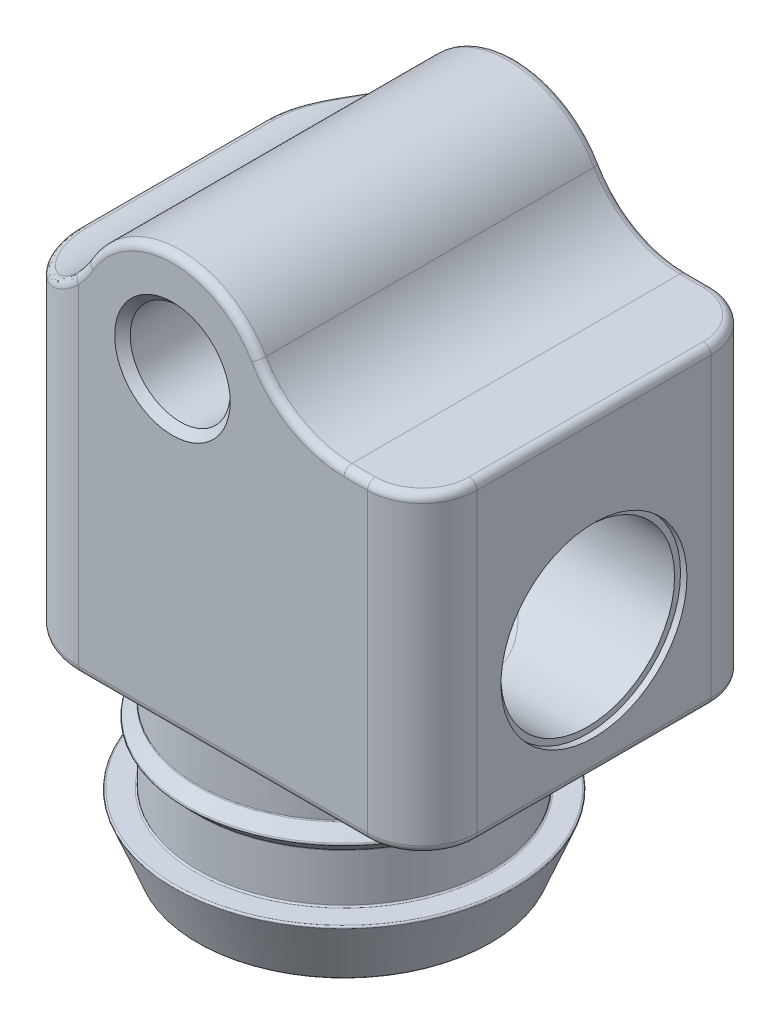
SolidWorks part; units mm, degrees
ref_plane "Front Plane" through (0, 0, 0) normal (0, 0, 1) x (1, 0, 0)
ref_plane "Top Plane" through (0, 0, 0) normal (0, 1, 0) x (1, 0, 0)
ref_plane "Right Plane" through (0, 0, 0) normal (1, 0, 0) x (0, 0, -1)
sketch "Sketch1" plane through (0, 0, 0) normal (0, 0, 1) x (1, 0, 0)
  line L4 (-11, 0) -> (-6.35, 0)
  line L5 (-11, 0) -> (-11, -20)
  line L6 (-11, -20) -> (16, -20)
  line L7 (16, 0) -> (16, -20)
  line L8 (6.35, 0) -> (16, 0)
  circle A0 centre (0, 0) radius 3.2
  arc A1 (6.35, 0) -> (-6.35, 0) centre (0, 0) ccw
  dimension "D1" = 6.4
  dimension "D2" = 12.7
  dimension "D3" = 11
  dimension "D4" = 16
  dimension "D5" = 20
extrude "Boss-Extrude1" add sketch "Sketch1" along normal mid plane 22
sketch3d "3DSketch1" plane through (0, 0, 0) normal (0, 0, 1) x (1, 0, 0)
  dimension "D1" = 12.7
sketch "Sketch2" plane through (0, 0, 0) normal (0, 0, 1) x (1, 0, 0)
  line L0 (0, 9.544) -> (0, -9.544) construction
  line L1 (0, -20) -> (9.365, -20)
  line L4 (0, -32.7) -> (9.365, -32.7)
  line L10 (0, -32.7) -> (0, -20)
  line L11 (9.365, -32.7) -> (10.9525, -28.7312)
  line L12 (10.9525, -28.7312) -> (9.365, -28.7312)
  line L13 (9.365, -28.7312) -> (9.365, -25.5563)
  line L14 (9.365, -25.5563) -> (10.1588, -24.7625)
  line L15 (10.1588, -24.7625) -> (9.365, -23.9688)
  line L16 (10.1588, -24.7625) -> (9.365, -24.7625) construction
  line L17 (9.365, -23.9688) -> (9.365, -20)
  dimension "D1" = 18.73
  dimension "D2" = 12.7
  dimension "D3" = 1.5875
  dimension "D4" = 3.9688
  dimension "D5" = 0.7937
  dimension "D6" = 7.9375
  dimension "D7" = 20
revolve "Revolve1" add sketch "Sketch2" angle 360 about L0
sketch "Sketch3" plane through (0, -32.7, 0) normal (0, -1, 0) x (1, 0, 0)
  circle A0 centre (0, 0) radius 6
  dimension "D1" = 12
extrude "Cut-Extrude1" cut sketch "Sketch3" against normal blind 27.25 contours A0
hole_wizard "1/4 NPT Tapped Hole1" positions "Sketch4" profile "Sketch5" size "1/4" standard "ANSI Inch" end condition up to next
sketch "Sketch4" plane through (16, 0, 0) normal (1, 0, 0) x (0, 0, -1)
  point P0 (0, -12)
  dimension "D1" = 12
cosmetic thread "Hole Thread1" parameters "D1"=0.4, "D2"=13.1394
sketch "Sketch5" plane through (16, -12, 0) normal (0, 1, 0) x (0, 0, -1)
  line L0 (0, 0) -> (0, 10)
  line L1 (0, 10) -> (5.5626, 10)
  line L2 (-5.9437, 0.4) -> (-5.9557, 0) construction
  line L3 (5.5626, 10) -> (5.5626, 0.4)
  line L4 (5.5626, 0.4) -> (5.9437, 0.4)
  line L5 (5.9437, 0.4) -> (5.9557, 0)
  line L7 (5.9557, 0) -> (0, 0)
  line L8 (0, -6.35) -> (0, 107.95) construction
  line L11 (-5.5626, 0.4) -> (-5.9437, 0.4) construction
  dimension "Thru Tap Drill Dia." = 11.1252
  dimension "Thru Tap Drill Depth" = 10
  dimension "Thread Dia." = 11.9113
  dimension "Thread Angle" = 3.43
  dimension "Thread Depth" = 0.4
fillet "Fillet3" radius 0.1 8 edges at (-10.9525, -28.7313, 0) (-10.1587, -24.7625, 0) (6, -5.45, 0) (-9.365, -32.7, 0) (-9.365, -25.5563, 0) (-9.365, -23.9688, 0) (-9.365, -28.7313, 0) (-9.365, -20, 0)
chamfer "Chamfer1" distance 0.5 angle 45 2 edges at (3.2, 0, -11) (3.2, 0, 11)
fillet "Fillet7" radius 6.35 2 edges at (-6.35, 0, 0) (6.35, 0, 0)
fillet "Fillet6" radius 3.5 2 edges at (16, -10, -11) (16, -10, 11)
fillet "Fillet12" radius 5 2 edges at (-11, -10, -11) (-11, -10, 11)
fillet "Fillet8" radius 0.5 24 edges at (-11, -20, 0) (3.25, -20, -11) (14.9749, -20, -9.9749) (16, -20, 0) (14.9749, -20, 9.9749) (14.9749, 0, 9.9749) (7.8235, 0.8507, 11) (0, 6.35, 11) (-5.7366, 2.7955, 11) (-11, 0, 0) (-5.7366, 2.7955, -11) (0, 6.35, -11) (7.8235, 0.8507, -11) (14.9749, 0, -9.9749) (3.25, -20, 11) (16, 0, 0) (11.7493, 0, 11) (11.7493, 0, -11) (6, -32.7, 0) (-9.6349, 0.1481, -9.4333) (-10.9996, 0, -6.0608) (-8.6524, 0.4493, 10.2385) (-9.5355, -20, 9.5355) (-9.5355, -20, -9.5355)
fillet "Fillet11" radius 3.5 1 edges at (5.9593, -17.5187, -0.6973)
